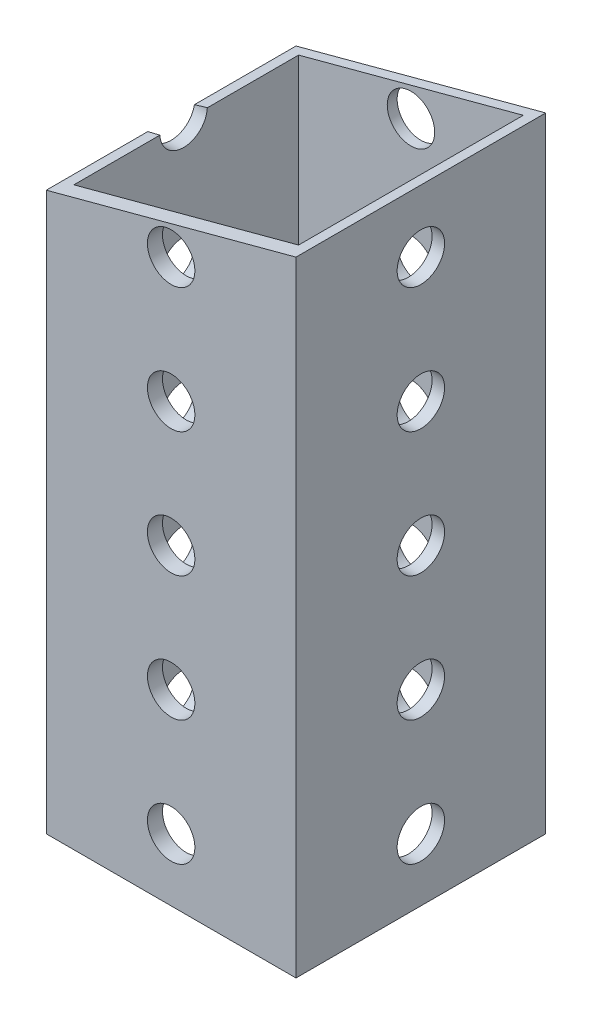
SolidWorks part; units mm, degrees
ref_plane "Front Plane" through (0, 0, 0) normal (0, 0, 1) x (1, 0, 0)
ref_plane "Top Plane" through (0, 0, 0) normal (0, 1, 0) x (1, 0, 0)
ref_plane "Right Plane" through (0, 0, 0) normal (1, 0, 0) x (0, 0, -1)
sketch "Sketch2" plane through (0, 0, 0) normal (0, 1, 0) x (1, 0, 0)
  line L1 (-12.7, -12.7) -> (12.7, -12.7)
  line L2 (-12.7, -12.7) -> (-12.7, 12.7)
  line L3 (-12.7, 12.7) -> (12.7, 12.7)
  line L4 (12.7, -12.7) -> (12.7, 12.7)
  line L7 (-11.43, -11.1675) -> (11.43, -11.1675)
  line L8 (-11.43, -11.1675) -> (-11.43, 11.6925)
  line L9 (-11.43, 11.6925) -> (11.43, 11.6925)
  line L10 (11.43, -11.1675) -> (11.43, 11.6925)
  point P0 (0, 0)
  point P6 (0, 0)
  dimension "D1" = 25.4
  dimension "D2" = 25.4
  dimension "D3" = 22.86
extrude "Boss-Extrude1" add sketch "Sketch2" along normal blind 63.5
sketch "Sketch3" plane through (0, 0, -12.7) normal (0, 0, -1) x (-1, 0, 0)
  line L0 (0, 63.5) -> (0, 0) construction
  line L1 (-12.7, 63.5) -> (12.7, 63.5) construction
  circle A0 centre (0, 57.15) radius 2.413
  circle A1 centre (0, 44.45) radius 2.413
  circle A2 centre (0, 31.75) radius 2.413
  circle A3 centre (0, 19.05) radius 2.413
  circle A4 centre (0, 6.35) radius 2.413
  circle A5 centre (0, -6.35) radius 2.413
  dimension "D1" = 4.826
  dimension "D2" = 6.35
  dimension "D3" = 6
extrude "Cut-Extrude1" cut sketch "Sketch3" against normal through all
sketch "Sketch4" plane through (12.7, 0, 0) normal (1, 0, 0) x (0, 0, -1)
  line L0 (0, 63.5) -> (0, 0) construction
  line L1 (-12.7, 63.5) -> (12.7, 63.5) construction
  circle A0 centre (0, 57.15) radius 2.413
  circle A1 centre (0, 44.45) radius 2.413
  circle A2 centre (0, 31.75) radius 2.413
  circle A3 centre (0, 19.05) radius 2.413
  circle A4 centre (0, 6.35) radius 2.413
  circle A5 centre (0, -6.35) radius 2.413
  dimension "D1" = 4.826
  dimension "D2" = 6.35
  dimension "D3" = 6
extrude "Cut-Extrude2" cut sketch "Sketch4" against normal through all
sketch "Sketch5" plane through (0, 0, 12.7) normal (0, 0, 1) x (1, 0, 0)
  line L0 (12.7, 63.5) -> (-12.7, 56.6941)
  line L1 (-12.7, 63.5) -> (-12.7, 0) construction
  line L2 (-12.7, 56.6941) -> (-12.7, 63.5)
  line L3 (-12.7, 63.5) -> (12.7, 63.5)
  dimension "D1" = 15
extrude "Cut-Extrude3" cut sketch "Sketch5" against normal through all
